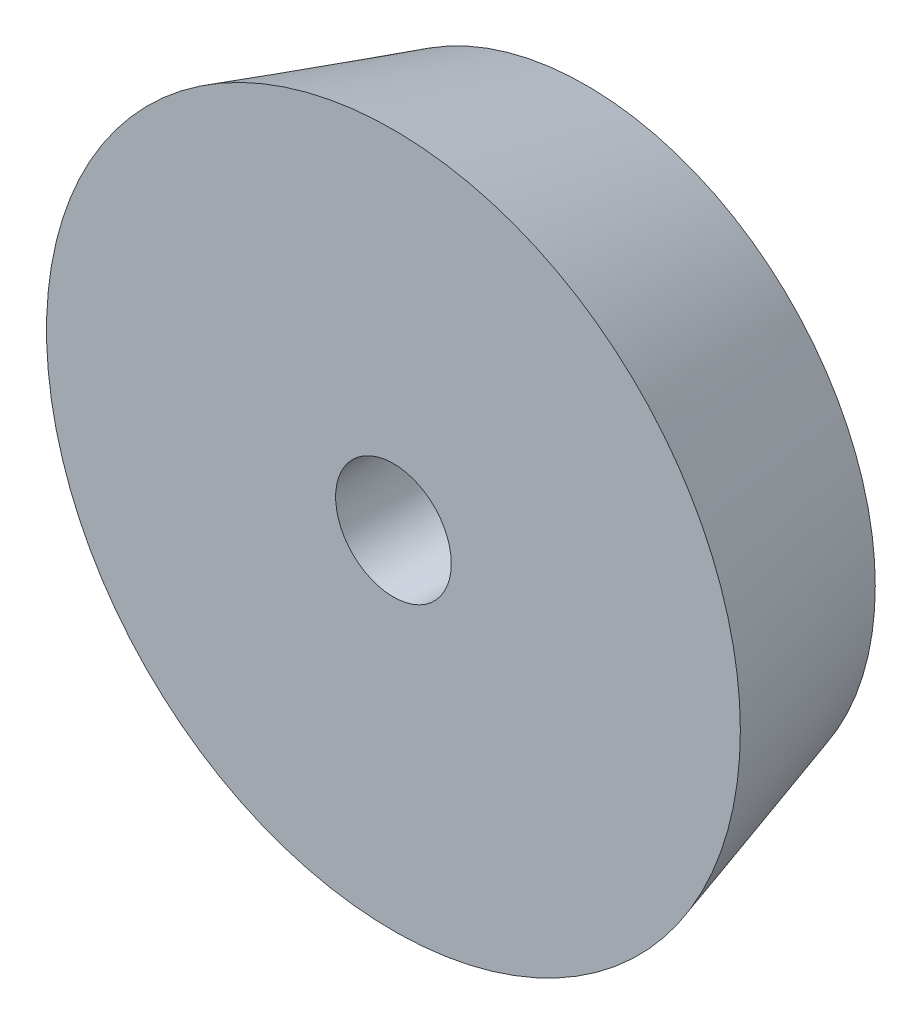
SolidWorks part; units mm, degrees
ref_plane "Front Plane" through (0, 0, 0) normal (0, 0, 1) x (1, 0, 0)
ref_plane "Top Plane" through (0, 0, 0) normal (0, 1, 0) x (1, 0, 0)
ref_plane "Right Plane" through (0, 0, 0) normal (1, 0, 0) x (0, 0, -1)
sketch "Sketch1" plane through (0, 0, 0) normal (0, 1, 0) x (1, 0, 0)
  line L0 (0, 0) -> (9, 0)
  line L1 (0, 0) -> (0, 5)
  line L2 (1.5, 0) -> (1.5, 5)
  line L3 (0, 5) -> (1.5, 5)
  line L4 (1.5, 5) -> (7.5, 5)
  line L5 (7.5, 5) -> (9, 0)
  dimension "D1" = 9
  dimension "D2" = 5
  dimension "D3" = 1.5
  dimension "D4" = 6
revolve "Revolve1" add sketch "Sketch1" angle 360 about L1 region at (4.8889, 0, -2.4074)
sketch "Sketch2" plane through (0, 0, -5) normal (0, 0, -1) x (-1, 0, 0)
  circle A0 centre (0, 0) radius 4.5
  dimension "D1" = 9
extrude "Cut-Extrude1" cut sketch "Sketch2" against normal blind 2
